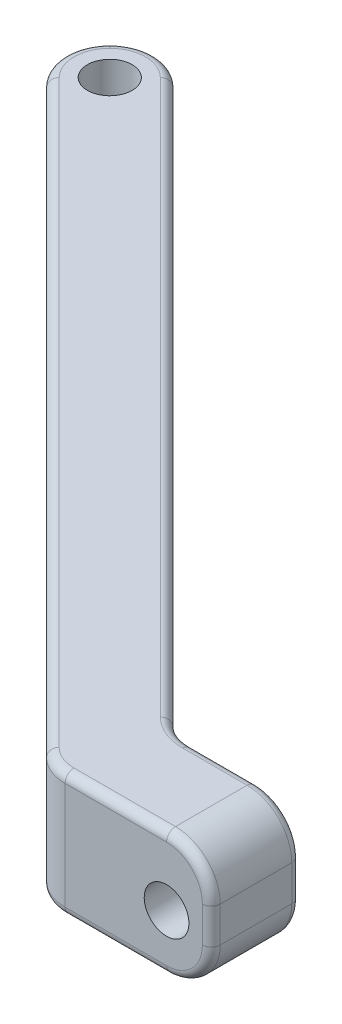
SolidWorks part; units mm, degrees
ref_plane "Front Plane" through (0, 0, 0) normal (0, 0, 1) x (1, 0, 0)
ref_plane "Top Plane" through (0, 0, 0) normal (0, 1, 0) x (1, 0, 0)
ref_plane "Right Plane" through (0, 0, 0) normal (1, 0, 0) x (0, 0, -1)
sketch "Sketch1" plane through (0, 0, 0) normal (0, 1, 0) x (1, 0, 0)
  line L0 (0, 7.0711) -> (-7.0711, 0)
  line L1 (0, 7.0711) -> (66.9211, -59.85)
  line L2 (-7.0711, 0) -> (62.7789, -69.85)
  line L4 (66.9211, -59.85) -> (81.2, -59.85)
  line L5 (81.2, -59.85) -> (81.2, -69.85)
  line L6 (81.2, -69.85) -> (62.7789, -69.85)
  circle A0 centre (0, 0) radius 2.5
  point P6 (76.2, -63.5)
  dimension "D1" = 5
  dimension "D2" = 5
  dimension "D3" = 5
  dimension "D4" = 10
  dimension "D5" = 69.85
  dimension "D6" = 45
  dimension "D7" = 10
  dimension "D8" = 5
  dimension "D9" = 76.2
  dimension "D10" = 63.5
extrude "Boss-Extrude1" add sketch "Sketch1" along normal blind 13.97
sketch "Sketch2" plane through (0, 0, 59.85) normal (0, 0, -1) x (-1, 0, 0)
  line L0 (-81.2, 13.97) -> (-81.2, 0) construction
  line L1 (-81.2, 0) -> (-66.9211, 0) construction
  circle A0 centre (-76.2, 6.35) radius 2.5
  dimension "D1" = 5
  dimension "D2" = 5
  dimension "D3" = 6.35
extrude "Cut-Extrude1" cut sketch "Sketch2" against normal up to next
fillet "Fillet1" radius 5 6 edges at (-7.0711, 6.985, 0) (0, 6.985, -7.0711) (81.2, 0, 64.85) (81.2, 13.97, 64.85) (62.7789, 6.985, 69.85) (66.9211, 6.985, 59.85)
fillet "Fillet2" radius 1 22 edges at (-5, 13.97, 0) (0, 13.97, -5) (34.4961, 13.97, 27.425) (67.0787, 13.97, 59.4694) (72.5961, 13.97, 59.85) (79.7355, 12.5055, 59.85) (81.2, 6.985, 59.85) (79.7355, 1.4645, 59.85) (72.5961, 0, 59.85) (67.0787, 0, 59.4694) (34.4961, 0, 27.425) (0, 0, -5) (-5, 0, 0) (28.8895, 0, 35.9605) (62.9366, 0, 69.4694) (70.525, 0, 69.85) (79.7355, 1.4645, 69.85) (81.2, 6.985, 69.85) (79.7355, 12.5055, 69.85) (70.525, 13.97, 69.85) (62.9366, 13.97, 69.4694) (28.8895, 13.97, 35.9605)
sketch "Sketch3" plane through (0, 0, 59.85) normal (0, 0, -1) x (-1, 0, 0)
  line L0 (-78.7259, 1.975) -> (-82.609, 1.975)
  line L1 (-73.6741, 1.975) -> (-71.1482, 6.35)
  line L2 (-71.1482, 6.35) -> (-73.6741, 10.725)
  line L3 (-73.6741, 10.725) -> (-78.7259, 10.725)
  line L4 (-78.7259, 10.725) -> (-81.2518, 6.35)
  line L5 (-81.2518, 6.35) -> (-78.7259, 1.975)
  line L6 (-78.7259, 1.975) -> (-73.6741, 1.975)
  line L7 (-82.609, 1.975) -> (-82.609, 10.725)
  line L8 (-82.609, 10.725) -> (-78.7259, 10.725)
  circle A0 centre (-76.2, 6.35) radius 4.375 construction
  dimension "D1" = 8.75
